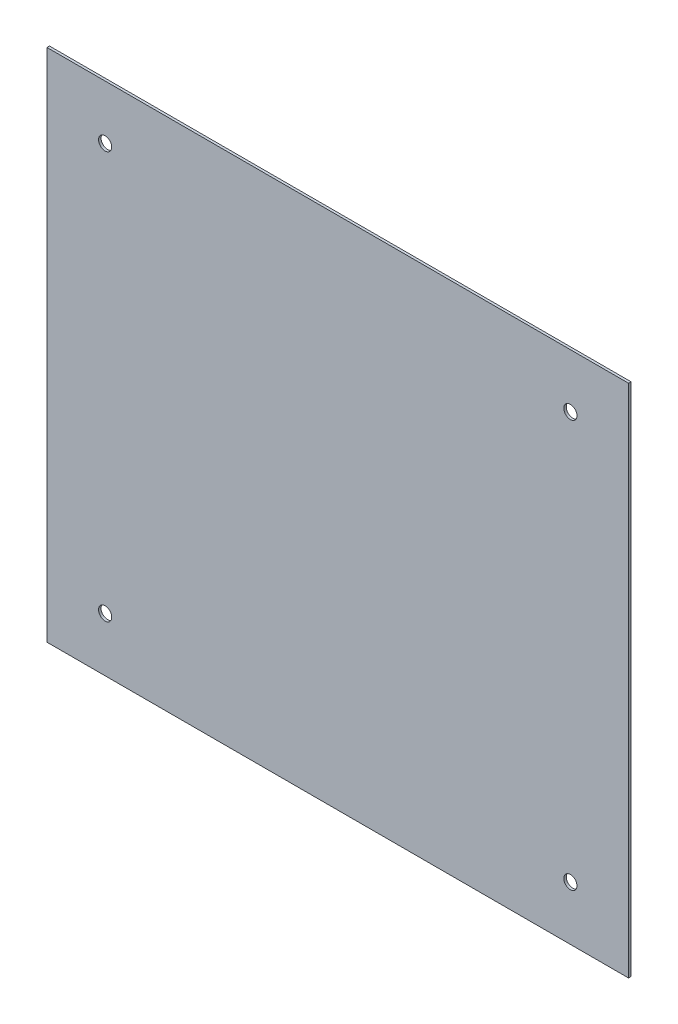
SolidWorks part; units mm, degrees
material "AISI 4130 Steel, annealed at 865C"
ref_plane "Front Plane" through (0, 0, 0) normal (0, 0, 1) x (1, 0, 0)
ref_plane "Top Plane" through (0, 0, 0) normal (0, 1, 0) x (1, 0, 0)
ref_plane "Right Plane" through (0, 0, 0) normal (1, 0, 0) x (0, 0, -1)
sketch "Sketch1" plane through (0, 0, 0) normal (0, 0, 1) x (1, 0, 0)
  line L1 (175, -155) -> (-175, -155)
  line L2 (175, -155) -> (175, 155)
  line L3 (175, 155) -> (-175, 155)
  line L4 (-175, -155) -> (-175, 155)
  line L5 (175, -155) -> (-175, 155) construction
  line L6 (175, 155) -> (-175, -155) construction
  point P0 (0, 0)
  dimension "D1" = 310
  dimension "D2" = 350
extrude "Boss-Extrude1" add sketch "Sketch1" along normal blind 1.5
sketch "Sketch3" plane through (0, 0, 1.5) normal (0, 0, 1) x (1, 0, 0)
  line L0 (-175, 155) -> (-175, -155) construction
  line L1 (175, 155) -> (-175, 155) construction
  line L2 (175, -155) -> (175, 155) construction
  line L3 (-175, -155) -> (175, -155) construction
  circle A0 centre (-140, 122.5) radius 3.97
  circle A1 centre (140, 122.5) radius 3.97
  circle A2 centre (-140, -122.5) radius 3.97
  circle A3 centre (140, -122.5) radius 3.97
  dimension "D1" = 7.94
  dimension "D4" = 7.94
  dimension "D6" = 35
  dimension "D7" = 7.94
  dimension "D8" = 7.94
  dimension "D9" = 35
  dimension "D10" = 35
  dimension "D11" = 32.5
  dimension "D12" = 32.5
  dimension "D2" = 35
  dimension "D3" = 32.5
  dimension "D5" = 32.5
extrude "Cut-Extrude1" cut sketch "Sketch3" against normal blind 10 and the other way blind 10
